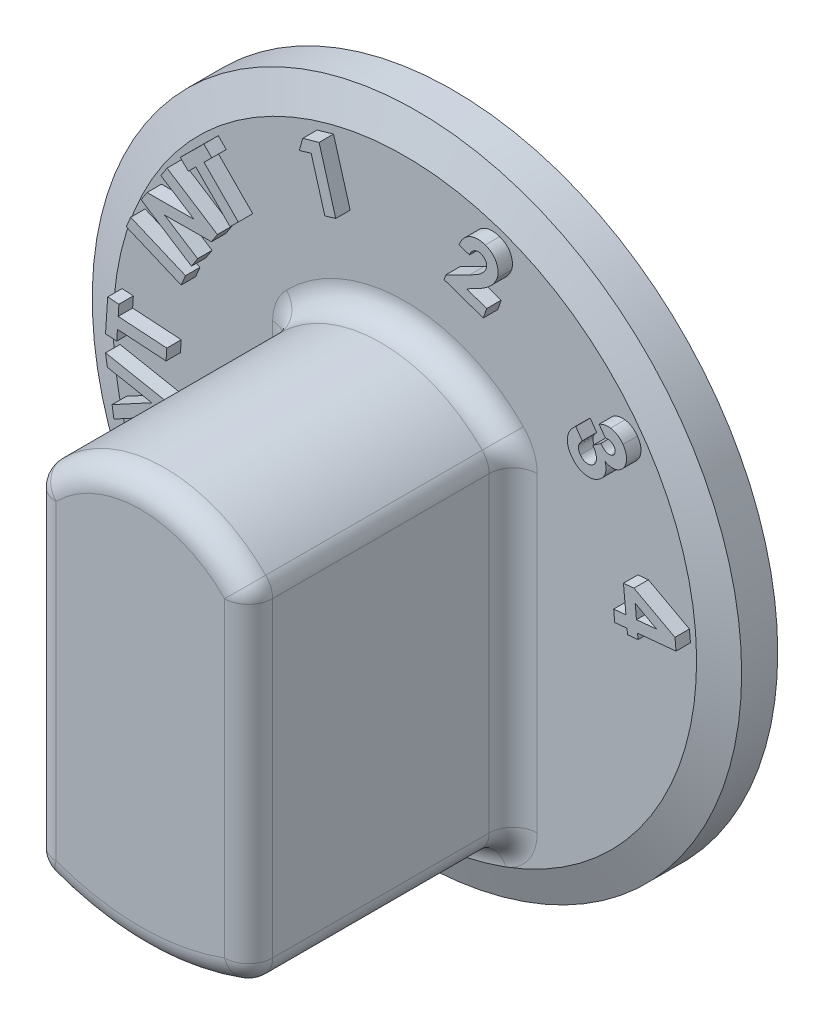
SolidWorks part; units mm, degrees
ref_plane "Front Plane" through (0, 0, 0) normal (0, 0, 1) x (1, 0, 0)
ref_plane "Top Plane" through (0, 0, 0) normal (0, 1, 0) x (1, 0, 0)
ref_plane "Right Plane" through (0, 0, 0) normal (1, 0, 0) x (0, 0, -1)
sketch "Sketch1" plane through (0, 0, 0) normal (0, 0, 1) x (1, 0, 0)
  circle A0 centre (0, 0) radius 13.5
  dimension "D1" = 27
extrude "Boss-Extrude1" add sketch "Sketch1" along normal blind 2 contours A0 region at (0, 0, 0)
chamfer "Chamfer1" distance 0.5 angle 70 1 edges at (13.5, 0, 2) first distance on face at (13.5, 0, 2)
sketch "Sketch2" plane through (0, 0, 2) normal (0, 0, 1) x (1, 0, 0)
  line L0 (0, 12.1263) -> (0, -12.1263) construction
  line L1 (-4.5, 3.4372) -> (-4.5, -9.5022)
  line L2 (4.5, 3.4372) -> (4.5, -9.5022)
  line L3 (4.5, 12.1263) -> (4.5, -12.1263) construction
  line L4 (-4.5, 12.1263) -> (-4.5, -12.1263) construction
  circle A2 centre (0, 0) radius 12.1263 construction
  circle A3 centre (0, 0) radius 12.1263 construction
  arc A4 (-3.8456, -10.4405) -> (3.8456, -10.4405) centre (0, 0) ccw
  circle A5 centre (0, 0) radius 11.1263 construction
  arc A6 (-4.2135, 4.1379) -> (4.2135, 4.1379) centre (0, 0) cw
  arc A7 (4.5, 3.4372) -> (4.2135, 4.1379) centre (3.5, 3.4372) ccw
  arc A8 (-4.5, 3.4372) -> (-4.2135, 4.1379) centre (-3.5, 3.4372) cw
  arc A9 (4.5, -9.5022) -> (3.8456, -10.4405) centre (3.5, -9.5022) cw
  arc A10 (-4.5, -9.5022) -> (-3.8456, -10.4405) centre (-3.5, -9.5022) ccw
  point P21 (-4.5, 3.8244)
  point P26 (-4.5, -10.1756)
  dimension "D1" = 4.5
  dimension "D5" = 1
  dimension "D6" = 1
  dimension "D4" = 14
  dimension "D2" = 4.5
  dimension "D3" = 1
extrude "Boss-Extrude2" add sketch "Sketch2" along normal blind 11
fillet "Fillet1" radius 1 16 edges at (-4.4256, 3.8157, 2) (0, 5.9056, 2) (4.4256, 3.8157, 2) (4.5, -3.0325, 2) (4.3203, -10.0742, 2) (-4.3203, -10.0742, 2) (4.5, -3.0325, 13) (4.3203, -10.0742, 13) (0, -11.1263, 13) (-4.3203, -10.0742, 13) (-4.5, -3.0325, 13) (-4.4256, 3.8157, 13) (0, 5.9056, 13) (4.4256, 3.8157, 13) (-4.5, -3.0325, 2) (0, -11.1263, 2)
sketch "Sketch6" plane through (0, 0, 0) normal (0, 0, -1) x (-1, 0, 0)
  line L0 (0, 0) -> (0, 6.2989) construction
  line L1 (0, 0) -> (0, 2.75) construction
  arc A1 (-1.9413, 1.9478) -> (-2.2553, 1.5736) centre (0, 0) ccw
  arc A2 (0.2351, 2.7399) -> (-0.2351, 2.7399) centre (0, 2.825) ccw
  arc A3 (1.158, 2.4943) -> (0.7162, 2.6551) centre (0.9662, 2.6546) ccw
  arc A4 (1.9413, 1.9478) -> (1.5811, 2.25) centre (1.8159, 2.1641) ccw
  arc A5 (2.4904, 1.1664) -> (2.2553, 1.5736) centre (2.4465, 1.4125) ccw
  arc A6 (2.7391, 0.2443) -> (2.6575, 0.7073) centre (2.7821, 0.4906) ccw
  arc A7 (2.6575, -0.7073) -> (2.7391, -0.2443) centre (2.7821, -0.4906) ccw
  arc A8 (2.2553, -1.5736) -> (2.4904, -1.1664) centre (2.4465, -1.4125) ccw
  arc A9 (1.5811, -2.25) -> (1.9413, -1.9478) centre (1.8159, -2.1641) ccw
  arc A10 (0.7162, -2.6551) -> (1.158, -2.4943) centre (0.9662, -2.6546) ccw
  arc A11 (-0.2351, -2.7399) -> (0.2351, -2.7399) centre (0, -2.825) ccw
  arc A12 (-1.158, -2.4943) -> (-0.7162, -2.6551) centre (-0.9662, -2.6546) ccw
  arc A13 (-1.9413, -1.9478) -> (-1.5811, -2.25) centre (-1.8159, -2.1641) ccw
  arc A14 (-2.4904, -1.1664) -> (-2.2553, -1.5736) centre (-2.4465, -1.4125) ccw
  arc A15 (-2.7391, -0.2443) -> (-2.6575, -0.7073) centre (-2.7821, -0.4906) ccw
  arc A16 (-2.6575, 0.7073) -> (-2.7391, 0.2443) centre (-2.7821, 0.4906) ccw
  arc A17 (-2.2553, 1.5736) -> (-2.4904, 1.1664) centre (-2.4465, 1.4125) ccw
  arc A18 (-1.5811, 2.25) -> (-1.9413, 1.9478) centre (-1.8159, 2.1641) ccw
  arc A19 (-0.7162, 2.6551) -> (-1.158, 2.4943) centre (-0.9662, 2.6546) ccw
  arc A20 (-1.158, 2.4943) -> (-1.5811, 2.25) centre (0, 0) ccw
  arc A21 (-0.2351, 2.7399) -> (-0.7162, 2.6551) centre (0, 0) ccw
  arc A22 (0.7162, 2.6551) -> (0.2351, 2.7399) centre (0, 0) ccw
  arc A23 (1.5811, 2.25) -> (1.158, 2.4943) centre (0, 0) ccw
  arc A24 (2.2553, 1.5736) -> (1.9413, 1.9478) centre (0, 0) ccw
  arc A25 (2.6575, 0.7073) -> (2.4904, 1.1664) centre (0, 0) ccw
  arc A26 (2.7391, -0.2443) -> (2.7391, 0.2443) centre (0, 0) ccw
  arc A27 (2.4904, -1.1664) -> (2.6575, -0.7073) centre (0, 0) ccw
  arc A28 (1.9413, -1.9478) -> (2.2553, -1.5736) centre (0, 0) ccw
  arc A29 (1.158, -2.4943) -> (1.5811, -2.25) centre (0, 0) ccw
  arc A30 (0.2351, -2.7399) -> (0.7162, -2.6551) centre (0, 0) ccw
  arc A31 (-0.7162, -2.6551) -> (-0.2351, -2.7399) centre (0, 0) ccw
  arc A32 (-1.5811, -2.25) -> (-1.158, -2.4943) centre (0, 0) ccw
  arc A33 (-2.2553, -1.5736) -> (-1.9413, -1.9478) centre (0, 0) ccw
  arc A34 (-2.6575, -0.7073) -> (-2.4904, -1.1664) centre (0, 0) ccw
  arc A35 (-2.7391, 0.2443) -> (-2.7391, -0.2443) centre (0, 0) ccw
  arc A36 (-2.4904, 1.1664) -> (-2.6575, 0.7073) centre (0, 0) ccw
  point P43 (0, 3.075)
  point P60 (0, -3.075)
  dimension "D1" = 5.5
  dimension "D3" = 0.5
  dimension "D2" = 2.825
  dimension "D4" = 3.075
  dimension "D5" = 6.15
extrude "Hueco" cut sketch "Sketch6" against normal blind 9.5
sketch "Sketch7" plane through (0, 0, 2) normal (0, 0, 1) x (1, 0, 0)
  line L5 (0, 0) -> (-13.5, 0) construction
  line L6 (0, 0) -> (-10.9217, 7.9351) construction
  line L7 (0, 0) -> (-4.1717, 12.8393) construction
  line L9 (0, 0) -> (10.9217, 7.9351) construction
  line L10 (0, 0) -> (13.5, 0) construction
  line L71 (0, 0) -> (4.1717, 12.8393) construction
  circle A0 centre (0, 0) radius 9.3639 construction
  circle A1 centre (0, 0) radius 13.5 construction
  text T0 "<b>PVT  INT   1    2    3   4</b>" font "Century Gothic" height 2.5
  point P1 (0, 0)
  point P11 (0, 0)
  point P14 (0, 0)
  point P17 (0, 0)
  point P120 (0, 0)
  point P325 (-3.9229, 8.7176)
  point P326 (2.2192, 9.2699)
  point P327 (6.2416, 13.7314)
  point P328 (13.8964, 5.8649)
  point P329 (0, 0)
  point P330 (14.8038, 2.5243)
  dimension "D2" = 36
  dimension "D1" = 6
extrude "Textos" add sketch "Sketch7" along normal mid plane 1.2
sketch "Sketch8" plane through (0, 0, 0) normal (0, 0, -1) x (-1, 0, 0)
  circle A0 centre (0, 0) radius 3.5
  dimension "D1" = 7
extrude "Cut-Extrude1" cut sketch "Sketch8" against normal blind 0.6
